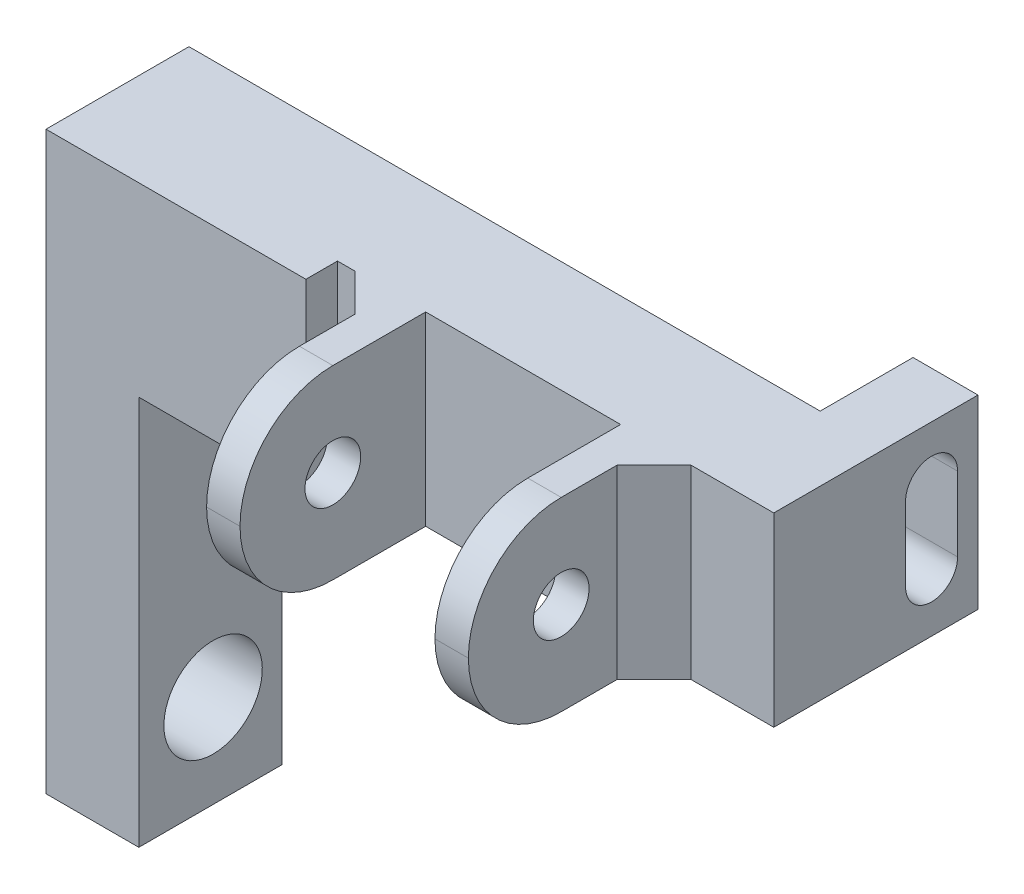
SolidWorks part; units mm, degrees
ref_plane "Front Plane" through (0, 0, 0) normal (0, 0, 1) x (1, 0, 0)
ref_plane "Top Plane" through (0, 0, 0) normal (0, 1, 0) x (1, 0, 0)
ref_plane "Right Plane" through (0, 0, 0) normal (1, 0, 0) x (0, 0, -1)
sketch "Sketch1" plane through (0, 0, 0) normal (0, 0, 1) x (1, 0, 0)
  line L1 (10, -15) -> (-10, -15)
  line L2 (10, -15) -> (10, 15)
  line L3 (10, 15) -> (-10, 15)
  line L4 (-10, -15) -> (-10, 15)
  line L5 (10, -15) -> (-10, 15) construction
  line L6 (10, 15) -> (-10, -15) construction
  circle A0 centre (0, -10) radius 2.65
  circle A1 centre (0, 0) radius 2.65
  point P0 (0, 0)
  dimension "D3" = 5.3
  dimension "D4" = 5.3
  dimension "D5" = 5
  dimension "D6" = 10
  dimension "D1" = 20
  dimension "D2" = 30
extrude "Boss-Extrude1" add sketch "Sketch1" along normal blind 3
sketch "Sketch2" plane through (0, 0, 3) normal (0, 0, 1) x (1, 0, 0)
  line L0 (10, -15) -> (10, 15) construction
  line L1 (-10, 15) -> (10, 15)
  line L2 (-10, 15) -> (-10, 5)
  line L3 (-10, 5) -> (10, 5)
  line L4 (10, 15) -> (10, 5)
  dimension "D1" = 10
extrude "Boss-Extrude2" add sketch "Sketch2" along normal blind 3
sketch "Sketch3" plane through (0, 0, 6) normal (0, 0, 1) x (1, 0, 0)
  line L0 (10, 15) -> (-10, 15) construction
  line L1 (-7.05, 15) -> (-5.25, 15)
  line L2 (-7.05, 15) -> (-7.05, 5)
  line L3 (-7.05, 5) -> (-5.25, 5)
  line L4 (-5.25, 15) -> (-5.25, 5)
  line L5 (-10, 5) -> (10, 5) construction
  line L6 (-10, 15) -> (-10, 5) construction
  line L7 (5.25, 15) -> (7.05, 15)
  line L8 (5.25, 15) -> (5.25, 5)
  line L9 (5.25, 5) -> (7.05, 5)
  line L10 (7.05, 15) -> (7.05, 5)
  dimension "D1" = 10.5
  dimension "D2" = 1.8
  dimension "D3" = 2.95
extrude "Boss-Extrude3" add sketch "Sketch3" along normal blind 10
fillet "Fillet1" radius 5 4 edges at (6.15, 5, 16) (-6.15, 5, 16) (6.15, 15, 16) (-6.15, 15, 16)
sketch "Sketch4" plane through (-7.05, 0, 0) normal (-1, 0, 0) x (0, 0, 1)
  circle A0 centre (11, 10) radius 1.5
  arc A1 (16, 10) -> (11, 15) centre (11, 10) ccw construction
  dimension "D1" = 3
extrude "Cut-Extrude1" cut sketch "Sketch4" against normal up to surface (14.1 mm away) up to face at (7.05, 10, 10.4142)
chamfer "Chamfer1" distance 2 angle 45 2 edges at (7.05, 10, 6) (-7.05, 10, 6)
sketch "Sketch5" plane through (0, 0, 3) normal (0, 0, 1) x (1, 0, 0)
  line L1 (-10, -15) -> (10, -15)
  line L2 (-10, -15) -> (-10, 5)
  line L3 (-10, 5) -> (10, 5)
  line L4 (10, -15) -> (10, 5)
extrude "Cut-Extrude2" cut sketch "Sketch5" against normal blind 10
sketch "Sketch6" plane through (10, 0, 0) normal (1, 0, 0) x (0, 0, -1)
  line L0 (-6, 5) -> (0, 5) construction
  line L1 (-6, 15) -> (5, 15)
  line L2 (-6, 15) -> (-6, 5)
  line L3 (-6, 5) -> (5, 5)
  line L4 (5, 15) -> (5, 5)
  line L5 (0, 5) -> (0, 15) construction
  dimension "D1" = 5
extrude "Boss-Extrude4" add sketch "Sketch6" along normal blind 3.5
sketch "Sketch7" plane through (13.5, 0, 0) normal (1, 0, 0) x (0, 0, -1)
  line L1 (2.5, 8) -> (2.5, 12) construction
  line L3 (1.1, 8) -> (1.1, 12)
  line L4 (3.9, 8) -> (3.9, 12)
  arc A1 (1.1, 8) -> (3.9, 8) centre (2.5, 8) ccw
  arc A2 (3.9, 12) -> (1.1, 12) centre (2.5, 12) ccw
  point P4 (2.5, 10)
  dimension "D1" = 1.4
  dimension "D4" = 4
extrude "Cut-Extrude3" cut sketch "Sketch7" against normal blind 3.5
sketch "Sketch8" plane through (-10, 0, 0) normal (-1, 0, 0) x (0, 0, 1)
  line L1 (7.7, 15) -> (0, 15)
  line L2 (7.7, 15) -> (7.7, -16)
  line L3 (7.7, -16) -> (0, -16)
  line L4 (0, 15) -> (0, -16)
  line L5 (0, 15) -> (0, 5) construction
  circle A0 centre (3.7, -11) radius 2.65
  circle A1 centre (11, 10) radius 1.5 construction
  dimension "D1" = 7.3
  dimension "D2" = 4
  dimension "D3" = 5.3
  dimension "D4" = 21
  dimension "D5" = 5
extrude "Boss-Extrude5" add sketch "Sketch8" along normal blind 14
sketch "Sketch9" plane through (0, 0, 7.7) normal (0, 0, 1) x (1, 0, 0)
  line L0 (-24, -16) -> (-24, 15) construction
  line L1 (-10, -16) -> (-19, -16)
  line L2 (-10, -16) -> (-10, 5)
  line L3 (-10, 5) -> (-19, 5)
  line L4 (-19, -16) -> (-19, 5)
  line L5 (-10, 5) -> (-9.05, 5) construction
  dimension "D1" = 5
extrude "Cut-Extrude4" cut sketch "Sketch9" against normal blind 10
